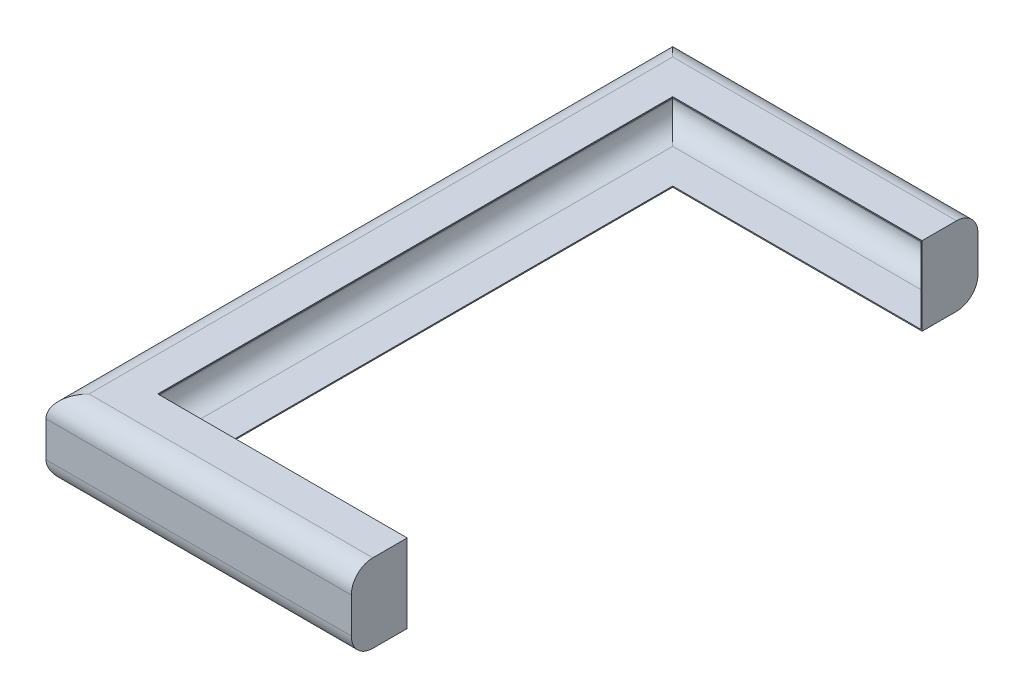
SolidWorks part; units mm, degrees
ref_plane "Front" through (0, 0, 0) normal (0, 0, 1) x (1, 0, 0)
ref_plane "Top" through (0, 0, 0) normal (0, 1, 0) x (1, 0, 0)
ref_plane "Right" through (0, 0, 0) normal (1, 0, 0) x (0, 0, -1)
sketch "Sketch1" plane through (0, 0, 0) normal (0, 1, 0) x (1, 0, 0)
  line L0 (368.3, 380.2126) -> (0, 380.2126)
  line L1 (0, 380.2126) -> (0, -380.2126)
  line L2 (0, -380.2126) -> (368.3, -380.2126)
  line L3 (368.3, -380.2126) -> (368.3, -462.7626)
  line L4 (368.3, -462.7626) -> (-82.55, -462.7626)
  line L5 (-82.55, -462.7626) -> (-82.55, 462.7626)
  line L6 (-82.55, 462.7626) -> (368.3, 462.7626)
  line L7 (368.3, 462.7626) -> (368.3, 380.2126)
  point P3 (0, 0)
  dimension "D1" = 82.55
  dimension "D2" = 82.55
  dimension "D3" = 760.4252
  dimension "D4" = 450.85
extrude "Boss-Extrude1" add sketch "Sketch1" along normal mid plane 115.8875
fillet "Fillet1" radius 31.75 6 edges at (142.875, -57.9437, 462.7626) (-82.55, -57.9437, 0) (142.875, -57.9437, -462.7626) (142.875, 57.9437, -462.7626) (-82.55, 57.9437, 0) (142.875, 57.9437, 462.7626)
shell "Shell1" thickness 1.5875 removed face at (184.15, 0, -380.2126) removed face at (184.15, 0, 380.2126) removed face at (0, 0, 0)
